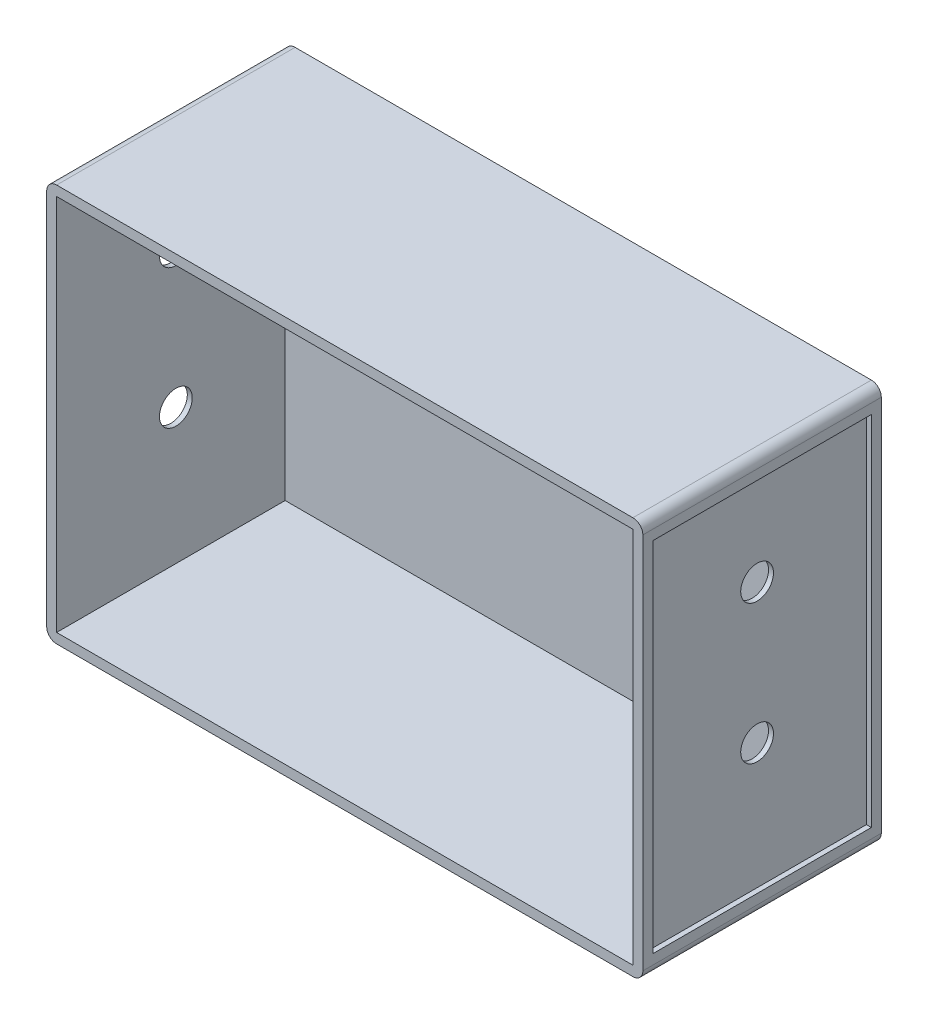
SolidWorks part; units mm, degrees
ref_plane "Front Plane" through (0, 0, 0) normal (0, 0, 1) x (1, 0, 0)
ref_plane "Top Plane" through (0, 0, 0) normal (0, 1, 0) x (1, 0, 0)
ref_plane "Right Plane" through (0, 0, 0) normal (1, 0, 0) x (0, 0, -1)
sketch "Sketch1" plane through (0, 0, 0) normal (0, 0, 1) x (1, 0, 0)
  line L1 (-150, 100) -> (150, 100)
  line L2 (-150, 100) -> (-150, -100)
  line L3 (-150, -100) -> (150, -100)
  line L4 (150, 100) -> (150, -100)
  line L5 (-150, 100) -> (150, -100) construction
  line L6 (-150, -100) -> (150, 100) construction
  point P0 (0, 0)
  dimension "D1" = 300
  dimension "D2" = 200
extrude "Boss-Extrude1" add sketch "Sketch1" along normal mid plane 120
fillet "Fillet1" radius 5 4 edges at (150, -100, 0) (-150, -100, 0) (-150, 100, 0) (150, 100, 0)
shell "Shell1" thickness 5 removed face at (0, 0, 60)
sketch "Sketch5" plane through (150, 0, 0) normal (1, 0, 0) x (0, 0, -1)
  line L8 (-55, 90) -> (-55, -90)
  line L9 (-55, -90) -> (55, -90)
  line L10 (55, -90) -> (55, 90)
  line L11 (55, 90) -> (-55, 90)
  line L12 (-55, 90) -> (-55, -90)
  line L13 (-55, -90) -> (55, -90)
  line L14 (55, -90) -> (55, 90)
  line L15 (55, 90) -> (-55, 90)
  dimension "D1" = 5
extrude "Cut-Extrude1" cut sketch "Sketch5" against normal blind 2.5
sketch "Sketch6" plane through (-150, 0, 0) normal (-1, 0, 0) x (0, 0, 1)
  line L8 (-55, 90) -> (-55, -90)
  line L9 (-55, -90) -> (55, -90)
  line L10 (55, -90) -> (55, 90)
  line L11 (55, 90) -> (-55, 90)
  line L12 (-55, 90) -> (-55, -90)
  line L13 (-55, -90) -> (55, -90)
  line L14 (55, -90) -> (55, 90)
  line L15 (55, 90) -> (-55, 90)
  dimension "D1" = 5
extrude "Cut-Extrude2" cut sketch "Sketch6" against normal blind 2.5
sketch "Sketch7" plane through (-147.5, 0, 0) normal (-1, 0, 0) x (0, 0, 1)
  line L0 (0, 90) -> (0, -90) construction
  line L1 (55, 90) -> (-55, 90) construction
  line L2 (-55, -90) -> (55, -90) construction
  circle A0 centre (0, 43.1553) radius 8.25
  circle A1 centre (0, -26.8447) radius 8.25
  dimension "D1" = 16.5
  dimension "D2" = 70
extrude "Cut-Extrude3" cut sketch "Sketch7" against normal through all
